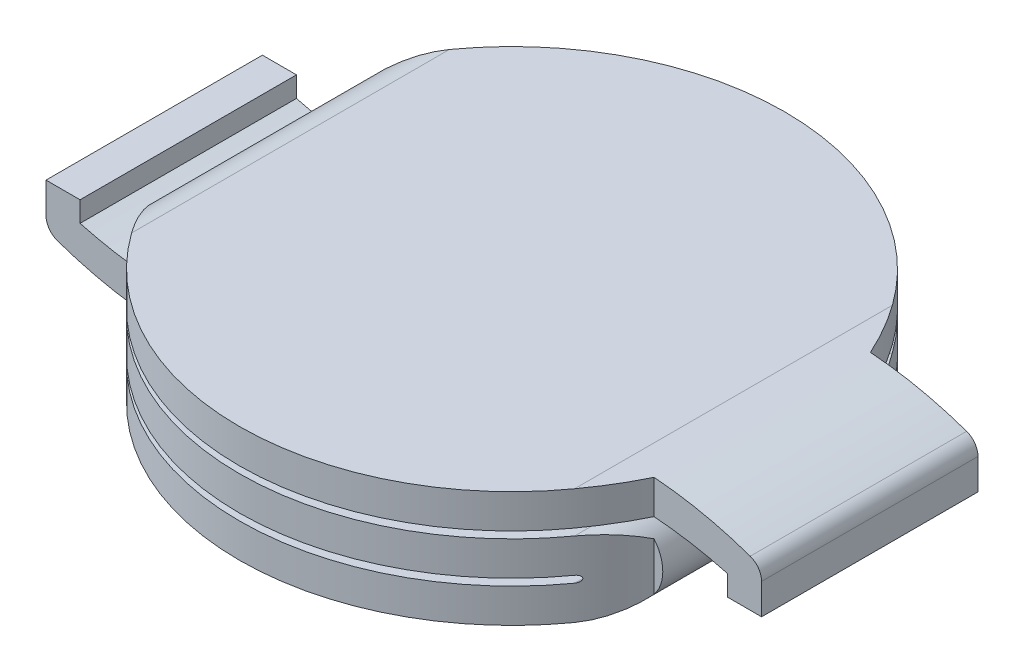
SolidWorks part; units mm, degrees
ref_plane "Front Plane" through (0, 0, 0) normal (0, 0, 1) x (1, 0, 0)
ref_plane "Top Plane" through (0, 0, 0) normal (0, 1, 0) x (1, 0, 0)
ref_plane "Right Plane" through (0, 0, 0) normal (1, 0, 0) x (0, 0, -1)
sketch "Sketch1" plane through (0, 0, 0) normal (0, 0, 1) x (1, 0, 0)
  line L0 (-6.5, 0) -> (6.5, 0)
  line L1 (-6.5, 1.2) -> (6.5, 1.2)
  line L2 (6.5, -1.2) -> (-6.5, -1.2)
  line L3 (6.5, -1.7) -> (-6.5, -1.7)
  line L4 (-6.5, 0.5) -> (6.5, 0.5)
  line L5 (-6.5, 0.7) -> (6.5, 0.7)
  line L6 (6.5, -0.7) -> (-6.5, -0.7)
  line L7 (-6.5, -0.5) -> (6.5, -0.5)
  line L8 (-6.5, 1.7) -> (6.5, 1.7)
  line L16 (-9.5, -0.3) -> (-9.5, 0.3)
  line L18 (-10.5, 0.3) -> (-10.5, -0.602)
  line L19 (-9.5, 0.3) -> (-10.5, 0.3)
  line L22 (10.5, 0.602) -> (10.5, -0.3)
  line L23 (10.5, -0.3) -> (9.5, -0.3)
  line L24 (9.5, 0.3) -> (9.5, -0.3)
  arc A0 (6.5, 0) -> (6.5, -1.2) centre (6.5, -0.6) cw
  arc A1 (-6.5, 0) -> (-6.5, 1.2) centre (-6.5, 0.6) cw
  arc A2 (6.5, 0.5) -> (6.5, -1.7) centre (6.5, -0.6) cw
  arc A3 (-6.5, 0.5) -> (-6.5, 0.7) centre (-6.5, 0.6) cw
  arc A4 (6.5, -0.5) -> (6.5, -0.7) centre (6.5, -0.6) cw
  arc A5 (-6.5, -0.5) -> (-6.5, 1.7) centre (-6.5, 0.6) cw
  arc A7 (6.5, 1.7) -> (10.166, 1.0736) centre (6.5, -9.3417) cw
  arc A8 (-6.5, -0.7) -> (-9.5, -0.3) centre (-6.5, 10.75) cw
  arc A9 (6.5, 0.7) -> (9.5, 0.3) centre (6.5, -10.75) cw
  arc A10 (-6.5, -1.7) -> (-10.166, -1.0736) centre (-6.5, 9.3417) cw
  arc A11 (-10.166, -1.0736) -> (-10.5, -0.602) centre (-10, -0.602) cw
  arc A12 (10.5, 0.602) -> (10.166, 1.0736) centre (10, 0.602) ccw
  point P4 (0, 0)
  point P9 (-10, 0.3)
  point P34 (10, -0.3)
  point P44 (10, -0.3)
  point P46 (-10, 0.3)
  point P49 (-10.5, -0.95)
  point P52 (10.5, 0.95)
  dimension "D3" = 0.5
  dimension "D4" = 0.6
  dimension "D2" = 0.6
  dimension "D16" = 0.5
  dimension "D1" = 13
  dimension "D6" = 1
  dimension "D7" = 10
  dimension "D8" = 0.6
  dimension "D9" = 0.3
  dimension "D10" = 10
  dimension "D11" = 0.6
  dimension "D12" = 0.3
  dimension "D13" = 1
  dimension "D14" = 1.25
  dimension "D15" = 1.25
  dimension "D5" = 0.5
extrude "Boss-Extrude1" add sketch "Sketch1" along normal blind 16 contours L5 A9 A7 L8 A5 L7 A4 L6 A8 L3 A2 L4 A3 region at (0, -1.4873, 0)
sketch "Sketch2" plane through (0, 1.7, 0) normal (0, 1, 0) x (1, 0, 0)
  line L5 (-10.5, -16) -> (-10.5, 0) construction
  line L6 (-5.5, -11.175) -> (-10.5, -11.175)
  line L7 (0, 0) -> (0, -16) construction
  line L8 (5.5, -4.825) -> (10.5, -11.175) construction
  line L9 (5.5, -11.175) -> (10.5, -4.825) construction
  line L19 (-5.5, -11.175) -> (-5.5, -4.825)
  line L20 (-5.5, -4.825) -> (-10.5, -4.825)
  line L21 (-10.5, -11.175) -> (-10.5, -4.825)
  line L22 (-5.5, -11.175) -> (-10.5, -4.825) construction
  line L23 (-5.5, -4.825) -> (-10.5, -11.175) construction
  line L24 (10.5, -11.175) -> (10.5, -4.825)
  line L25 (5.5, -4.825) -> (10.5, -4.825)
  line L26 (5.5, -11.175) -> (5.5, -4.825)
  line L27 (5.5, -11.175) -> (10.5, -11.175)
  circle A0 centre (0, -8) radius 8
  circle A1 centre (0, -8) radius 16.202
  point P3 (-8, -8)
  point P4 (-8, -8)
  point P16 (8, -8)
  line M7 (6.5, 0) -> (-6.5, 0)
  line M8 (-6.5, 0) -> (-6.5, -16)
  line M9 (-6.5, -16) -> (6.5, -16)
  line M10 (6.5, -16) -> (6.5, 0)
  dimension "D1" = 16
  dimension "D2" = 6.35
extrude "Cut-Extrude2" cut sketch "Sketch2" against normal blind 16 and the other way blind 16 contours A1 A0 L20 L25 L24 L27 M10 M9 M8 M7 | A0 M8 M9 | A0 M9 M10 | A0 M7 M8 | A0 M10 M7 region at (-4.9505, 1.7, 15.0489) region at (-4.9505, 1.7, 0.9511) region at (4.9505, 1.7, 15.0489) region at (4.9505, 1.7, 0.9511) region at (-15.7437, 1.7, 8)
